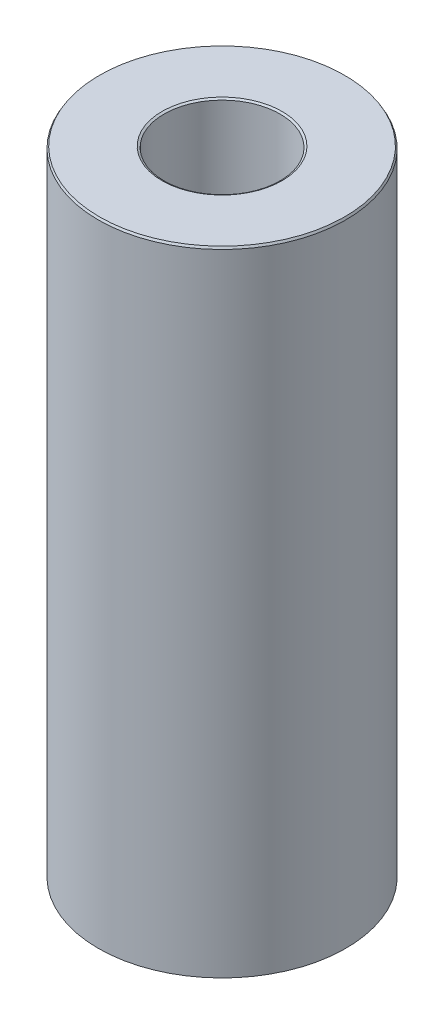
SolidWorks part; units mm, degrees
ref_plane "Front Plane" through (0, 0, 0) normal (0, 0, 1) x (1, 0, 0)
ref_plane "Top Plane" through (0, 0, 0) normal (0, 1, 0) x (1, 0, 0)
ref_plane "Right Plane" through (0, 0, 0) normal (1, 0, 0) x (0, 0, -1)
sketch "Sketch1" plane through (0, 0, 0) normal (0, 1, 0) x (1, 0, 0)
  circle A0 centre (0, 0) radius 57.5
  dimension "SLEEVE_OD" = 115
extrude "Boss-Extrude1" add sketch "Sketch1" along normal blind 294.5048
sketch "Sketch2" plane through (0, 0, 0) normal (0, 1, 0) x (1, 0, 0)
  circle A0 centre (0, 0) radius 26.9252
  dimension "BORE_D" = 53.8503
extrude "Cut-Extrude1" cut sketch "Sketch2" along normal through all
chamfer "Chamfer1" distance 0.9567 angle 30 4 edges at (0, 294.5048, 26.9252) (0, 0, 26.9252) (0, 0, 57.5) (0, 294.5048, 57.5) first distance on face at (0, 294.5048, 26.9252) first distance on face at (0, 0, 26.9252) first distance on face at (0, 294.5048, 57.5)
